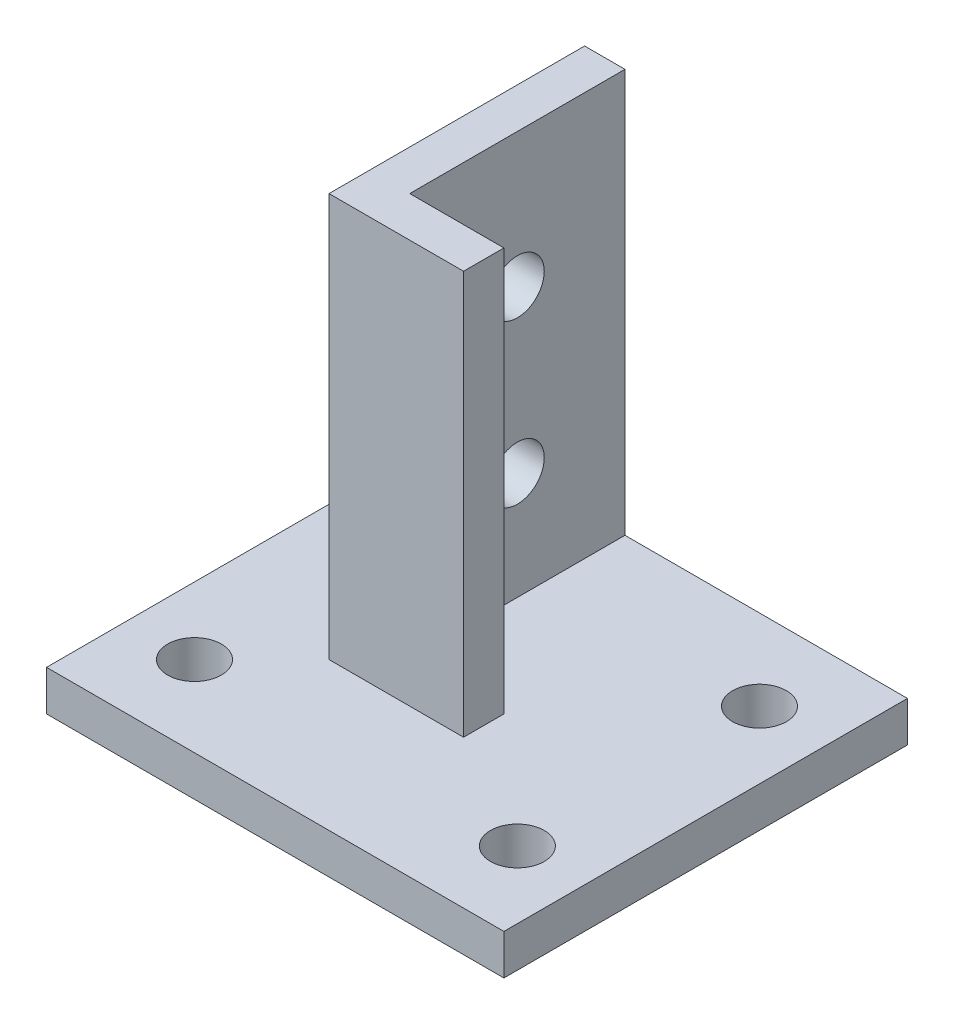
SolidWorks part; units mm, degrees
ref_plane "Front Plane" through (0, 0, 0) normal (0, 0, 1) x (1, 0, 0)
ref_plane "Top Plane" through (0, 0, 0) normal (0, 1, 0) x (1, 0, 0)
ref_plane "Right Plane" through (0, 0, 0) normal (1, 0, 0) x (0, 0, -1)
sketch "Sketch1" plane through (-298.9537, 0, -67.3536) normal (0, 1, 0) x (1, 0, 0)
  line L10 (298.9537, -37.3536) -> (298.9537, -67.3536)
  line L11 (298.9537, -67.3536) -> (332.9537, -67.3536)
  line L12 (332.9537, -67.3536) -> (332.9537, -37.3536)
  line L13 (332.9537, -37.3536) -> (298.9537, -37.3536)
  point P0 (4.8985, 3.5053)
  dimension "D1" = 34
  dimension "D4" = 30
extrude "Boss-Extrude1" add sketch "Sketch1" along normal blind 3
sketch "Sketch2" plane through (0, 0, -27) normal (0, -1, 0) x (1, 0, 0)
  line L0 (34, -3) -> (0, -3) construction
  line L5 (0, -3) -> (0, 27) construction
  circle A1 centre (5, 3) radius 2
  dimension "D1" = 4
  dimension "D2" = 6
  dimension "D3" = 5
extrude "Cut-Extrude1" cut sketch "Sketch2" against normal up to surface (3 mm away) up to face at (17, 3, -15)
pattern_linear "LPattern1" count 2 spacing 18 along (0, 0, 1) count 2 spacing 24 along (1, 0, 0) of "Cut-Extrude1"
ref_plane "Plane1" through (17, 0, 0) normal (1, 0, 0) x (0, 0, -1)
sketch "Sketch3" plane through (0, 3, -33) normal (0, 1, 0) x (1, 0, 0)
  line L0 (10, -3) -> (10, -22)
  line L1 (34, -3) -> (0, -3) construction
  line L2 (10, -22) -> (20, -22)
  line L3 (20, -22) -> (20, -19)
  line L4 (20, -19) -> (13, -19)
  line L5 (13, -19) -> (13, -3)
  line L6 (17, -34.65) -> (17, -31.35) construction
  line L7 (10, -3) -> (13, -3)
  dimension "D1" = 3
  dimension "D2" = 4
  dimension "D3" = 3
  dimension "D4" = 3
  dimension "D5" = 16
extrude "Boss-Extrude2" add sketch "Sketch3" along normal blind 30
sketch "Sketch4" plane through (13, 0, 0) normal (1, 0, 0) x (0, 0, -1)
  line L0 (14, 3) -> (30, 3) construction
  line L1 (14, 33) -> (14, 3) construction
  circle A0 centre (22, 23) radius 2
  circle A1 centre (22, 11) radius 2
  point P8 (0, 0)
  dimension "D4" = 4
  dimension "D1" = 12
  dimension "D2" = 8
  dimension "D3" = 8
extrude "Cut-Extrude2" cut sketch "Sketch4" against normal up to surface (3 mm away) up to face at (10, 18, -20.5)
